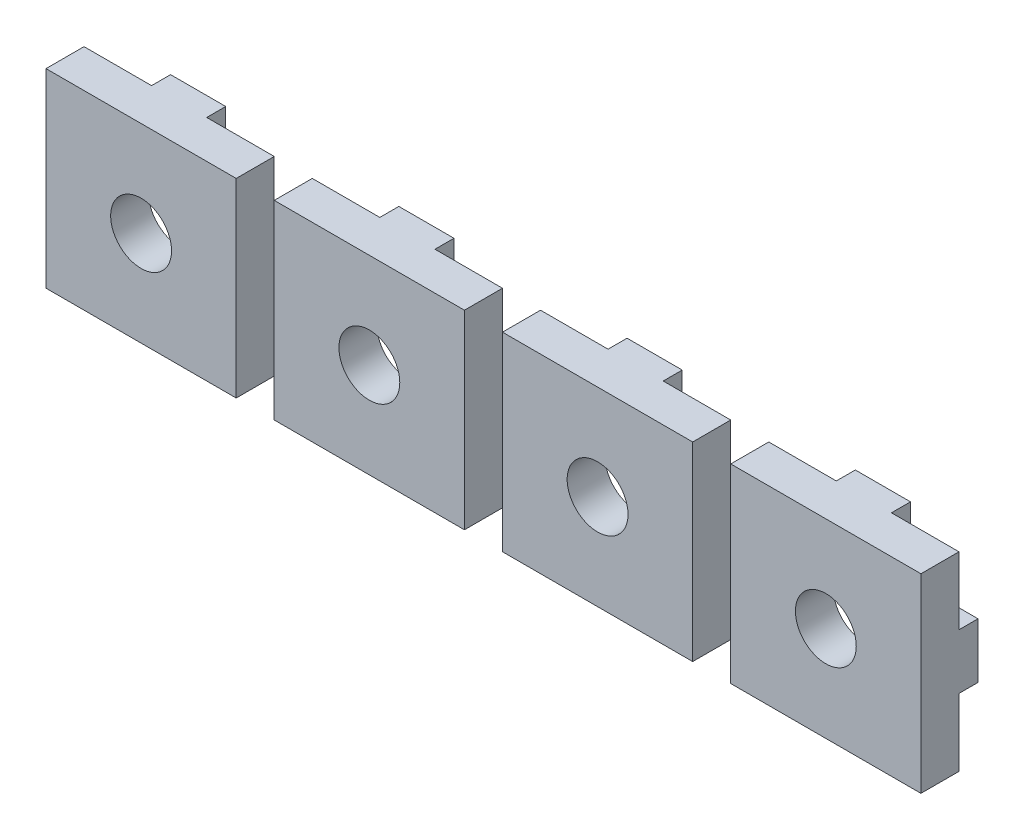
SolidWorks part; units mm, degrees
ref_plane "Front Plane" through (0, 0, 0) normal (0, 0, 1) x (1, 0, 0)
ref_plane "Top Plane" through (0, 0, 0) normal (0, 1, 0) x (1, 0, 0)
ref_plane "Right Plane" through (0, 0, 0) normal (1, 0, 0) x (0, 0, -1)
ref_axis "Axis1" through (0, 0, -1.2) along (0, 0, 1)
sketch "Sketch1" plane through (0, 0, 0) normal (0, 0, 1) x (1, 0, 0)
  line L1 (-5, -5) -> (5, -5)
  line L2 (-5, -5) -> (-5, 5)
  line L3 (-5, 5) -> (5, 5)
  line L4 (5, -5) -> (5, 5)
  line L5 (-5, -5) -> (5, 5) construction
  line L6 (-5, 5) -> (5, -5) construction
  circle A0 centre (0, 0) radius 1.6
  point P0 (0, 0)
  dimension "D3" = 3.2
  dimension "D1" = 10
  dimension "D2" = 10
extrude "Main" add sketch "Sketch1" along normal blind 2
sketch "Sketch2" plane through (0, 0, 0) normal (0, 0, -1) x (-1, 0, 0)
  line L0 (-5, 1.45) -> (-4, 1.45)
  line L1 (-5, -5) -> (-5, 5) construction
  line L2 (-4, 1.45) -> (-4, -1.45)
  line L3 (-4, -1.45) -> (-5, -1.45)
  line L4 (-5, 1.45) -> (-5, -1.45)
  point P5 (-4, 0)
  dimension "D1" = 2.9
  dimension "D2" = 1
extrude "AntiRotationSystem" add sketch "Sketch2" along normal blind 1
pattern_circular "CirPattern1" count 4 over 360 about axis through (0, 0, -1.2) along (0, 0, 1) of "AntiRotationSystem"
pattern_linear "LPattern1" count 4 spacing 12 along (1, 0, 0) of bodies 103
